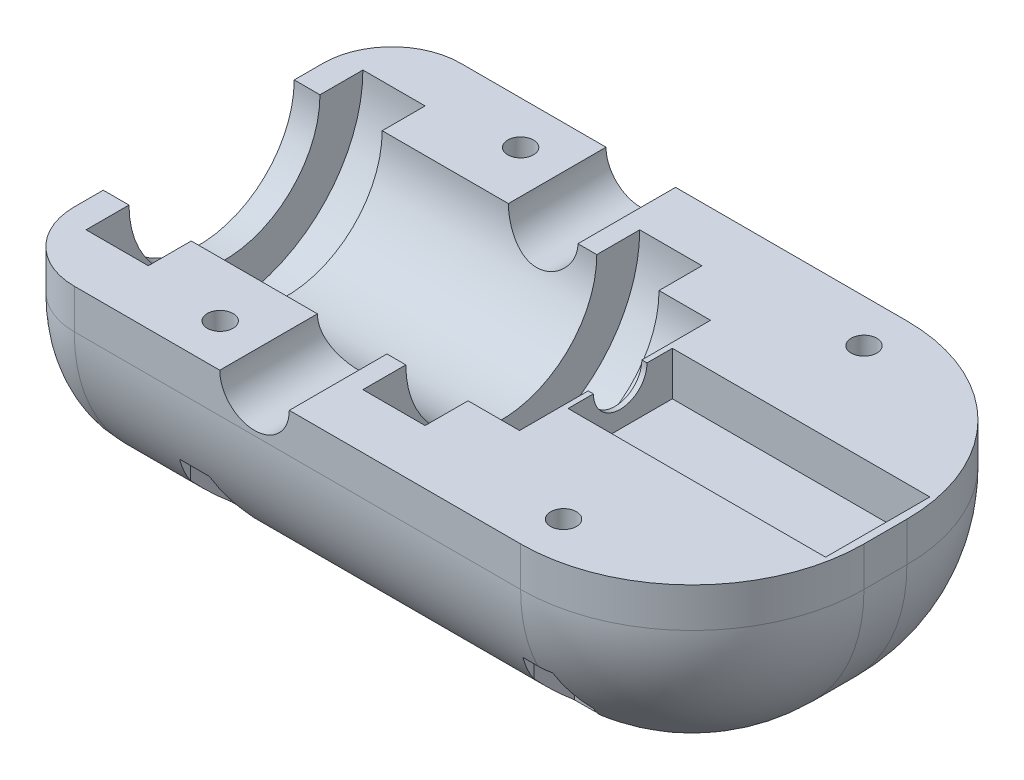
SolidWorks part; units mm, degrees
material "ABS PC"
ref_plane "Front Plane" through (0, 0, 0) normal (0, 0, 1) x (1, 0, 0)
ref_plane "Top Plane" through (0, 0, 0) normal (0, 1, 0) x (1, 0, 0)
ref_plane "Right Plane" through (0, 0, 0) normal (1, 0, 0) x (0, 0, -1)
sketch "Sketch1" plane through (0, 0, 0) normal (0, 1, 0) x (1, 0, 0)
  line L1 (-40, -22.5) -> (40, -22.5)
  line L2 (-40, -22.5) -> (-40, 22.5)
  line L3 (-40, 22.5) -> (40, 22.5)
  line L4 (40, -22.5) -> (40, 22.5)
  line L5 (-40, -22.5) -> (40, 22.5) construction
  line L6 (-40, 22.5) -> (40, -22.5) construction
  point P0 (0, 0)
  dimension "D1" = 45
  dimension "D2" = 80
extrude "Boss-Extrude1" add sketch "Sketch1" along normal blind 24.6
sketch "Sketch2" plane through (0, 24.6, 0) normal (0, 1, 0) x (1, 0, 0)
  line L0 (-40, 0) -> (40, 0) construction
  line L1 (-40, 22.5) -> (-40, -22.5) construction
  line L2 (40, -22.5) -> (40, 22.5) construction
  line L3 (8.5, 3.125) -> (9.5, 3.125)
  line L4 (-37, 11.125) -> (-37, 16.125)
  line L5 (-29.75, 11.125) -> (-29.75, 16.125)
  line L6 (-37, 16.125) -> (-29.75, 16.125)
  line L7 (9.5, 3.125) -> (9.5, 0)
  line L8 (-4.75, 11.125) -> (-4.75, 16.125)
  line L9 (2.5, 11.125) -> (2.5, 16.125)
  line L10 (-4.75, 16.125) -> (2.5, 16.125)
  line L11 (-40, 0) -> (-40, 11.125)
  line L12 (-40, 11.125) -> (-37, 11.125)
  line L13 (-29.75, 11.125) -> (-4.75, 11.125)
  line L14 (2.5, 11.125) -> (8.5, 11.125)
  line L15 (8.5, 11.125) -> (8.5, 3.125)
  line L16 (6, 0) -> (-40, 0)
  line L17 (40, 22.5) -> (-40, 22.5) construction
  line L18 (9.5, 0) -> (6, 0)
  dimension "D1" = 5
  dimension "D2" = 16.125
  dimension "D3" = 7.25
  dimension "D4" = 7.25
  dimension "D5" = 5
  dimension "D6" = 3
  dimension "D8" = 6
  dimension "D9" = 46
  dimension "D10" = 25
  dimension "D11" = 1
  dimension "D12" = 3.125
revolve "Cut-Revolve1" cut sketch "Sketch2" angle 360 about L0
sketch "Sketch3" plane through (0, 24.6, 0) normal (0, 1, 0) x (1, 0, 0)
  line L0 (8.5, -11.125) -> (8.5, -3.125) construction
  line L1 (9.1, -6.075) -> (39.1, -6.075)
  line L2 (9.1, -6.075) -> (9.1, 6.075)
  line L3 (9.1, 6.075) -> (39.1, 6.075)
  line L4 (39.1, -6.075) -> (39.1, 6.075)
  line L5 (9.1, -6.075) -> (39.1, 6.075) construction
  line L6 (9.1, 6.075) -> (39.1, -6.075) construction
  line L7 (40, -22.5) -> (40, 22.5) construction
  point P0 (24.1, 0)
  point P9 (40, 0)
  dimension "D1" = 12.15
  dimension "D2" = 30
  dimension "D3" = 0.6
extrude "Cut-Extrude1" cut sketch "Sketch3" against normal blind 5.1
sketch "Sketch4" plane through (0, 0, 22.5) normal (0, 0, 1) x (1, 0, 0)
  line L0 (-40, 24.6) -> (40, 24.6) construction
  line L2 (-40, 24.6) -> (-40, 0) construction
  circle A0 centre (-11, 24.6) radius 4.05
  dimension "D1" = 8.1
  dimension "D2" = 29
extrude "Cut-Extrude2" cut sketch "Sketch4" against normal through all contours A0
sketch "Sketch5" plane through (0, 24.6, 0) normal (0, 1, 0) x (1, 0, 0)
  line L0 (-40, -22.5) -> (-15.05, -22.5) construction
  line L1 (-15.05, 22.5) -> (-40, 22.5) construction
  line L2 (40, -22.5) -> (40, 22.5) construction
  line L3 (-40, 22.5) -> (-40, 11.125) construction
  circle A0 centre (-20, 17.5) radius 1.5
  circle A1 centre (-20, -17.5) radius 1.5
  circle A2 centre (20, -17.5) radius 1.5
  circle A3 centre (20, 17.5) radius 1.5
  point P14 (-40, 16.8125)
  dimension "D3" = 3
  dimension "D4" = 3
  dimension "D5" = 3
  dimension "D6" = 3
  dimension "D1" = 5
  dimension "D2" = 5
  dimension "D7" = 20
  dimension "D8" = 20
extrude "Cut-Extrude3" cut sketch "Sketch5" against normal blind 31
fillet "Fillet1" radius 20 2 edges at (0, 0, -22.5) (0, 0, 22.5)
fillet "Fillet2" radius 20 5 edges at (40, 22.3, 22.5) (40, 5.8579, 16.6421) (40, 0, 0) (40, 22.3, -22.5) (40, 5.8579, -16.6421)
sketch "Sketch6" plane through (0, 0, 0) normal (0, -1, 0) x (1, 0, 0)
  line L1 (21.7321, 20.5) -> (18.2679, 20.5)
  line L2 (18.2679, 20.5) -> (16.5359, 17.5)
  line L3 (16.5359, 17.5) -> (18.2679, 14.5)
  line L4 (18.2679, 14.5) -> (21.7321, 14.5)
  line L5 (21.7321, 14.5) -> (23.4641, 17.5)
  line L6 (23.4641, 17.5) -> (21.7321, 20.5)
  line L7 (-18.2679, 20.5) -> (-21.7321, 20.5)
  line L8 (-21.7321, 20.5) -> (-23.4641, 17.5)
  line L9 (-23.4641, 17.5) -> (-21.7321, 14.5)
  line L10 (-21.7321, 14.5) -> (-18.2679, 14.5)
  line L11 (-18.2679, 14.5) -> (-16.5359, 17.5)
  line L12 (-16.5359, 17.5) -> (-18.2679, 20.5)
  line L13 (-18.2679, -14.5) -> (-21.7321, -14.5)
  line L14 (-21.7321, -14.5) -> (-23.4641, -17.5)
  line L15 (-23.4641, -17.5) -> (-21.7321, -20.5)
  line L16 (-21.7321, -20.5) -> (-18.2679, -20.5)
  line L17 (-18.2679, -20.5) -> (-16.5359, -17.5)
  line L18 (-16.5359, -17.5) -> (-18.2679, -14.5)
  line L19 (21.7321, -14.5) -> (18.2679, -14.5)
  line L20 (18.2679, -14.5) -> (16.5359, -17.5)
  line L21 (16.5359, -17.5) -> (18.2679, -20.5)
  line L22 (18.2679, -20.5) -> (21.7321, -20.5)
  line L23 (21.7321, -20.5) -> (23.4641, -17.5)
  line L24 (23.4641, -17.5) -> (21.7321, -14.5)
  circle A0 centre (20, 17.5) radius 3 construction
  circle A1 centre (-20, 17.5) radius 3 construction
  circle A2 centre (-20, -17.5) radius 3 construction
  circle A3 centre (20, -17.5) radius 3 construction
  dimension "D1" = 6
  dimension "D2" = 6
  dimension "D3" = 6
  dimension "D4" = 6
extrude "Cut-Extrude4" cut sketch "Sketch6" against normal blind 14
fillet "Fillet3" radius 8 5 edges at (-40, 22.3, -22.5) (-40, 22.3, 22.5) (-40, 5.8579, 16.6421) (-40, 0, 0) (-40, 5.8579, -16.6421)
